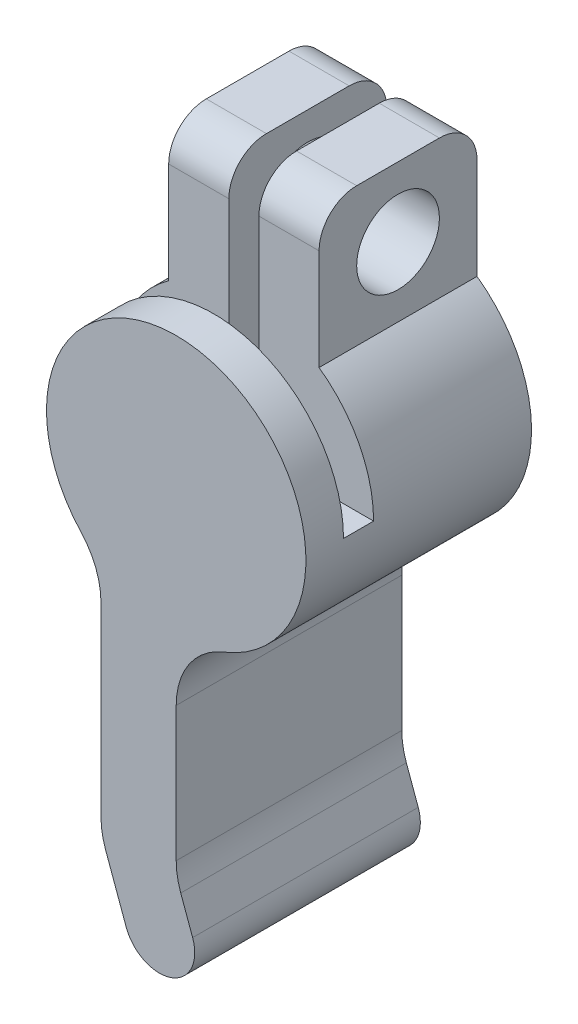
SolidWorks part; units mm, degrees
ref_plane "Front Plane" through (0, 0, 0) normal (0, 0, 1) x (1, 0, 0)
ref_plane "Top Plane" through (0, 0, 0) normal (0, 1, 0) x (1, 0, 0)
ref_plane "Right Plane" through (0, 0, 0) normal (1, 0, 0) x (0, 0, -1)
sketch "Sketch1" plane through (0, 0, 0) normal (0, 0, 1) x (1, 0, 0)
  line L0 (0, -9) -> (0, -3.45)
  line L1 (-2, -9) -> (-2, -2.8111)
  line L2 (0, -9) -> (0.4368, -10.2)
  line L4 (-1.3293, -10.8428) -> (-2, -9)
  line L5 (-2, -9) -> (0, -9) construction
  line L6 (-1.3293, -10.8428) -> (0.4368, -10.2) construction
  line L9 (-0.4, 1.3937) -> (-0.4, 6.5)
  line L10 (-0.4, 6.5) -> (-2, 6.5)
  line L11 (-2, 6.5) -> (-2, 2.8111)
  line L12 (0.4, 1.3937) -> (0.4, 6.5)
  line L13 (0.4, 6.5) -> (2, 6.5)
  line L14 (2, 6.5) -> (2, 2.8111)
  arc A0 (-0.4, 1.3937) -> (0.4, 1.3937) centre (0, 0) ccw
  arc A2 (0, -3.45) -> (2, 2.8111) centre (0, 0) ccw
  circle A4 centre (0, 0) radius 3.45 construction
  arc A5 (-1.3293, -10.8428) -> (0.4368, -10.2) centre (-0.4463, -10.5214) ccw
  arc A6 (-2, 2.8111) -> (-2, -2.8111) centre (0, 0) ccw
  circle A7 centre (0, 0) radius 1.45 construction
  point P3 (-1, -9)
  dimension "D1" = 2.9
  dimension "D4" = 1.2
  dimension "D6" = 160
  dimension "D7" = 0.8
  dimension "D2" = 2
  dimension "D3" = 9
  dimension "D8" = 1.6
  dimension "D9" = 6.5
  dimension "D5" = 2
extrude "Boss-Extrude1" add sketch "Sketch1" along normal blind 4.2 contours A2 A0 | A2 region at (0.0376, -9.6658, 0)
sketch "Sketch2" plane through (-2, 0, 0) normal (-1, 0, 0) x (0, 0, 1)
  line L0 (4.2, 6.5) -> (0, 6.5) construction
  line L7 (0, 6.5) -> (0, 2.8111) construction
  circle A0 centre (2.1, 4.6556) radius 1.1
  point P2 (2.1, 6.5)
  point P3 (0, 4.6556)
  point P6 (0, 0)
  dimension "D1" = 2.2
extrude "Cut-Extrude1" cut sketch "Sketch2" against normal through all
fillet "Fillet1" radius 1 4 edges at (1.2, 6.5, 4.2) (1.2, 6.5, 0) (-1.2, 6.5, 4.2) (-1.2, 6.5, 0)
sketch "Sketch3" plane through (0, 0, 4.2) normal (0, 0, 1) x (1, 0, 0)
  line L0 (-3.45, 0) -> (-1.45, 0)
  line L1 (1.45, 0) -> (3.45, 0)
  line L10 (2, 2.8111) -> (2, 5.5)
  line L11 (2, 5.5) -> (0.4, 5.5)
  line L12 (0.4, 5.5) -> (0.4, 1.3937)
  line L13 (-0.4, 1.3937) -> (-0.4, 5.5)
  line L14 (-0.4, 5.5) -> (-2, 5.5)
  line L15 (-2, 5.5) -> (-2, 2.8111)
  line L16 (-2, -2.8111) -> (-2, -9)
  line L17 (-2, -9) -> (-1.3293, -10.8428)
  line L18 (0.4368, -10.2) -> (0, -9)
  line L19 (0, -9) -> (0, -3.45)
  line L22 (0.4, 5.5) -> (0.4, 1.3937)
  line L26 (-2, -2.8111) -> (-2, -9)
  line L27 (-2, -9) -> (-1.3293, -10.8428)
  line L28 (0.4368, -10.2) -> (0, -9)
  line L29 (0, -9) -> (0, -3.45)
  arc A4 (-0.4, 1.3937) -> (0.4, 1.3937) centre (0, 0) ccw
  arc A5 (-2, 2.8111) -> (-2, -2.8111) centre (0, 0) ccw
  arc A6 (-1.3293, -10.8428) -> (0.4368, -10.2) centre (-0.4463, -10.5214) ccw
  arc A7 (0, -3.45) -> (2, 2.8111) centre (0, 0) ccw
  arc A8 (-1.45, 0) -> (1.45, 0) centre (0, 0) ccw
  arc A9 (-3.45, 0) -> (-2, -2.8111) centre (0, 0) ccw
  arc A10 (-1.3293, -10.8428) -> (0.4368, -10.2) centre (-0.4463, -10.5214) ccw
  arc A11 (0, -3.45) -> (3.45, 0) centre (0, 0) ccw
  arc M18 (0.4, 1.3937) -> (-0.4, 1.3937) centre (0, 0) cw
  arc M22 (-2, 2.8111) -> (-2, -2.8111) centre (0, 0) ccw
  line M23 (-2, -2.8111) -> (-2, -9)
  line M24 (-2, -9) -> (-1.3293, -10.8428)
  arc M25 (-1.3293, -10.8428) -> (0.4368, -10.2) centre (-0.4463, -10.5214) ccw
  line M26 (0.4368, -10.2) -> (0, -9)
  line M27 (0, -9) -> (0, -3.45)
  arc M28 (0, -3.45) -> (2, 2.8111) centre (0, 0) ccw
  dimension "D1" = 0
extrude "Boss-Extrude2" add sketch "Sketch3" along normal blind 0.8 contours L1 L0 M18 M22 M23 M24 M25 M26 M27 M28 region at (-0.4643, -4.4881, 4.2)
sketch "Sketch4" plane through (0, 0, 5) normal (0, 0, 1) x (1, 0, 0)
  line L4 (1.45, 0) -> (3.45, 0)
  line L5 (2, 2.8111) -> (2, 5.5)
  line L6 (3.45, 0) -> (1.45, 0)
  line L7 (-1.45, 0) -> (-3.45, 0)
  line L8 (-2, -2.8111) -> (-2, -9)
  line L9 (-2, -9) -> (-1.3293, -10.8428)
  line L10 (0.4368, -10.2) -> (0, -9)
  line L11 (0, -9) -> (0, -3.45)
  line L14 (-2, -2.8111) -> (-2, -9)
  line L15 (-2, -9) -> (-1.3293, -10.8428)
  line L16 (0.4368, -10.2) -> (0, -9)
  line L17 (0, -9) -> (0, -3.45)
  line L18 (2, 5.5) -> (0.4, 5.5)
  line L19 (0.4, 5.5) -> (0.4, 1.3937)
  line L24 (-3.45, 0) -> (-1.45, 0)
  line L25 (-0.4, 1.3937) -> (-0.4, 5.5)
  line L26 (-0.4, 5.5) -> (-2, 5.5)
  line L27 (-2, 5.5) -> (-2, 2.8111)
  arc A2 (3.45, 0) -> (2, 2.8111) centre (0, 0) ccw
  arc A3 (1.45, 0) -> (0.4, 1.3937) centre (0, 0) ccw
  arc A4 (-1.45, 0) -> (1.45, 0) centre (0, 0) ccw
  arc A5 (-3.45, 0) -> (-2, -2.8111) centre (0, 0) ccw
  arc A6 (-1.3293, -10.8428) -> (0.4368, -10.2) centre (-0.4463, -10.5214) ccw
  arc A7 (0, -3.45) -> (3.45, 0) centre (0, 0) ccw
  arc A8 (-1.45, 0) -> (1.45, 0) centre (0, 0) ccw
  arc A9 (-3.45, 0) -> (-2, -2.8111) centre (0, 0) ccw
  arc A10 (-1.3293, -10.8428) -> (0.4368, -10.2) centre (-0.4463, -10.5214) ccw
  arc A11 (0, -3.45) -> (3.45, 0) centre (0, 0) ccw
  arc A12 (3.45, 0) -> (2, 2.8111) centre (0, 0) ccw
  arc A13 (1.45, 0) -> (0.4, 1.3937) centre (0, 0) ccw
  arc A14 (-0.4, 1.3937) -> (-1.45, 0) centre (0, 0) ccw
  arc A15 (-2, 2.8111) -> (-3.45, 0) centre (0, 0) ccw
  arc A16 (0.4, 1.3937) -> (-1.45, 0) centre (0, 0) ccw
  arc A17 (2, 2.8111) -> (-3.45, 0) centre (0, 0) ccw
  line M23 (3.45, 0) -> (1.45, 0)
  arc M24 (1.45, 0) -> (-1.45, 0) centre (0, 0) cw
  line M25 (-1.45, 0) -> (-3.45, 0)
  arc M26 (-3.45, 0) -> (-2, -2.8111) centre (0, 0) ccw
  line M27 (-2, -2.8111) -> (-2, -9)
  line M28 (-2, -9) -> (-1.3293, -10.8428)
  arc M29 (-1.3293, -10.8428) -> (0.4368, -10.2) centre (-0.4463, -10.5214) ccw
  line M30 (0.4368, -10.2) -> (0, -9)
  line M31 (0, -9) -> (0, -3.45)
  arc M32 (0, -3.45) -> (3.45, 0) centre (0, 0) ccw
  dimension "D1" = 0
  dimension "D2" = 0
  dimension "D3" = 0
extrude "Boss-Extrude3" add sketch "Sketch4" along normal blind 1 contours A13 A16 M24 | A12 A17 A16 A13 M25 M23 | M32 M23 M24 M25 M26 M27 M28 M29 M30 M31 region at (1.8151, 1.5541, 5) region at (0, 0, 5) region at (-0.4643, -4.4881, 5) region at (0, 2.4368, 5) region at (-1.8151, 1.5541, 5)
fillet "Fillet2" radius 2 4 edges at (-2, -9, 3) (0, -9, 3) (0, -3.45, 3) (-2, -2.8111, 3)
